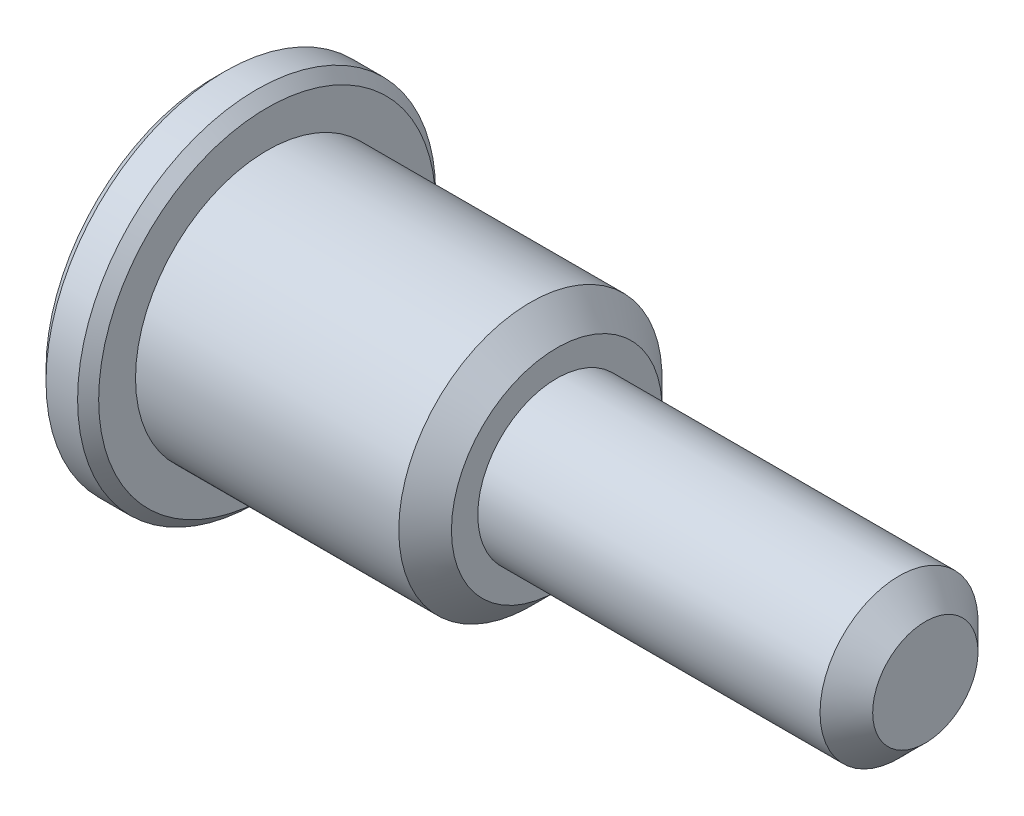
SolidWorks part; units mm, degrees
material "1Cr18Ni9Ti"
ref_plane "前视" through (0, 0, 0) normal (0, 0, 1) x (1, 0, 0)
ref_plane "上视" through (0, 0, 0) normal (0, 1, 0) x (1, 0, 0)
ref_plane "右视" through (0, 0, 0) normal (1, 0, 0) x (0, 0, -1)
sketch "草图1" plane through (0, 0, 0) normal (0, 0, 1) x (1, 0, 0)
  line L0 (0, 0) -> (13.1988, 0) construction
  line L1 (0, 0) -> (0, 3.4)
  line L2 (0, 3.4) -> (1, 3.4)
  line L3 (1, 3.4) -> (1, 2.5)
  line L4 (1, 2.5) -> (6.5, 2.5)
  line L5 (6.5, 2.5) -> (6.5, 1.5)
  line L6 (6.5, 1.5) -> (13.5, 1.5)
  line L7 (13.5, 1.5) -> (13.5, 0)
  line L8 (13.5, 0) -> (0, 0)
  dimension "D1" = 6.8
  dimension "D2" = 1
  dimension "D3" = 5
  dimension "D4" = 5.5
  dimension "D5" = 3
  dimension "D6" = 7
revolve "旋转1" add sketch "草图1" angle 360 about L0
chamfer "倒角1" distance 0.5 angle 45 2 edges at (6.5, 0, 2.5) (13.5, 0, 1.5)
chamfer "倒角2" distance 0.2 angle 45 2 edges at (1, 0, 3.4) (0, 0, 3.4)
